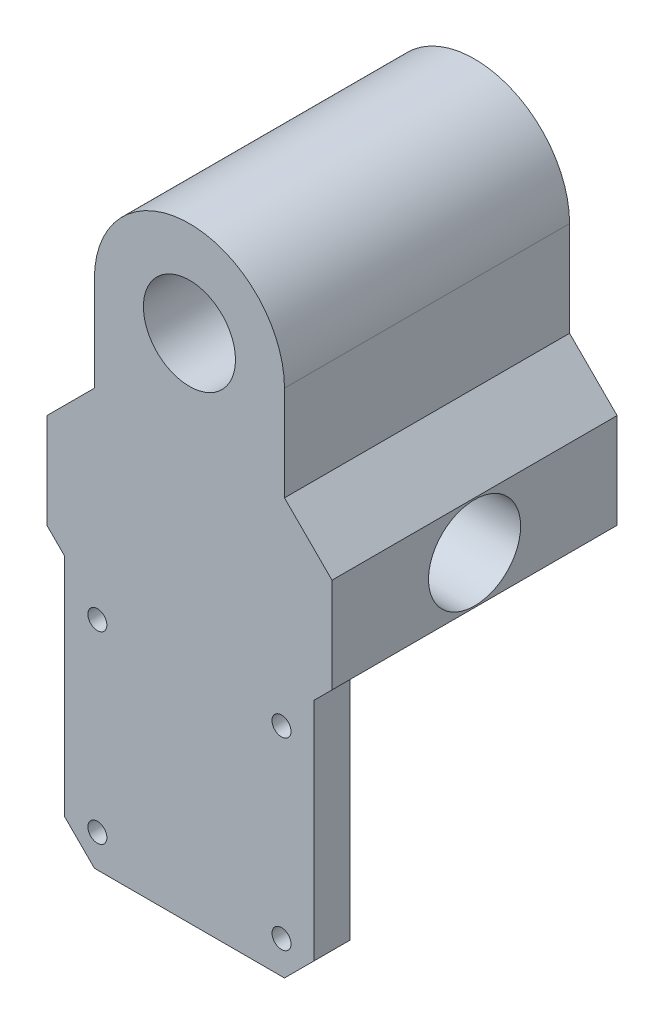
SolidWorks part; units mm, degrees
material "PET"
ref_plane "Front Plane" through (0, 0, 0) normal (0, 0, 1) x (1, 0, 0)
ref_plane "Top Plane" through (0, 0, 0) normal (0, 1, 0) x (1, 0, 0)
ref_plane "Right Plane" through (0, 0, 0) normal (1, 0, 0) x (0, 0, -1)
sketch "Sketch1" plane through (0, 0, 0) normal (0, 1, 0) x (1, 0, 0)
  line L0 (-24, 24) -> (24, -24) construction
  line L1 (-24, -24) -> (24, -24)
  line L2 (-24, -24) -> (-24, 24)
  line L3 (-24, 24) -> (24, 24)
  line L4 (24, -24) -> (24, 24)
  point P4 (0, 0)
  dimension "D1" = 48
  dimension "D2" = 48
extrude "Boss-Extrude1" add sketch "Sketch1" along normal blind 55 and the other way blind 5
sketch "Sketch2" plane through (0, 0, 24) normal (0, 0, 1) x (1, 0, 0)
  line L0 (0, 55) -> (0, 0) construction
  line L1 (-24, 55) -> (24, 55) construction
  circle A0 centre (0, 39) radius 7.75
  dimension "D1" = 15.5
  dimension "D2" = 16
extrude "Cut-Extrude1" cut sketch "Sketch2" against normal through all
sketch "Sketch3" plane through (24, 0, 0) normal (1, 0, 0) x (0, 0, -1)
  line L0 (0, 55) -> (0, 0) construction
  line L1 (-24, 55) -> (24, 55) construction
  circle A0 centre (0, 7) radius 7.75
  dimension "D1" = 15.5
  dimension "D2" = 48
extrude "Cut-Extrude2" cut sketch "Sketch3" against normal through all
sketch "Sketch6" plane through (0, 0, 24) normal (0, 0, 1) x (1, 0, 0)
  line L0 (-24, -5) -> (24, -5) construction
  line L1 (-21, -5) -> (21, -5)
  line L2 (-21, -5) -> (-21, -47)
  line L3 (-21, -47) -> (21, -47)
  line L4 (21, -5) -> (21, -47)
  point P7 (0, -5)
  dimension "D1" = 42
  dimension "D2" = 42
extrude "Boss-Extrude2" add sketch "Sketch6" against normal blind 6
sketch "Sketch7" plane through (0, 0, 18) normal (0, 0, -1) x (-1, 0, 0)
  line L0 (15.5, -41.5) -> (-15.5, -10.5) construction
  line L1 (-21, -5) -> (21, -47) construction
  line L2 (21, -47) -> (-21, -47) construction
  line L3 (21, -5) -> (21, -47) construction
  circle A0 centre (-15.5, -10.5) radius 1.6
  circle A1 centre (-15.5, -41.5) radius 1.6
  circle A2 centre (15.5, -41.5) radius 1.6
  circle A3 centre (15.5, -10.5) radius 1.6
  point P8 (0, -26)
  dimension "D1" = 3.2
  dimension "D2" = 3.2
  dimension "D3" = 3.2
  dimension "D4" = 3.2
  dimension "D5" = 31
  dimension "D6" = 31
extrude "Cut-Extrude4" cut sketch "Sketch7" against normal through all
sketch "Sketch9" plane through (0, 0, -24) normal (0, 0, -1) x (-1, 0, 0)
  line L0 (-1032, 23) -> (-16, 23) construction
  line L2 (-16, 39) -> (-16, 23)
  line L3 (-24, 55) -> (24, 55) construction
  line L4 (-16, 23) -> (-24, 23)
  line L5 (-24, -5) -> (-24, 55) construction
  line L6 (-24, 23) -> (-24, 55)
  line L7 (-24, 55) -> (24, 55)
  line L8 (24, 55) -> (24, 23)
  line L9 (24, -5) -> (24, 55) construction
  line L10 (16, 39) -> (16, 23)
  line L11 (16, 23) -> (24, 23)
  line L12 (16, 23) -> (1024, 23) construction
  arc A0 (16, 39) -> (-16, 39) centre (0, 39) ccw
  line M2 (24, -5) -> (24, 55)
  line M3 (24, 55) -> (-24, 55)
  line M4 (-24, 55) -> (-24, -5)
extrude "Cut-Extrude5" cut sketch "Sketch9" against normal through all contours A0 L7 L4 L2 M4 | A0 L10 L11 M2 M3 region at (-18.6618, 41.1955, -24) region at (18.6618, 41.1955, -24)
chamfer "Chamfer5" distance 8 angle 45 2 edges at (-24, 23, 0) (24, 23, 0)
chamfer "Chamfer7" distance 4 angle 45 2 edges at (-24, -5, 0) (24, -5, 0)
chamfer "Chamfer11" distance 5 angle 45 2 edges at (-21, -47, 21) (21, -47, 21)
